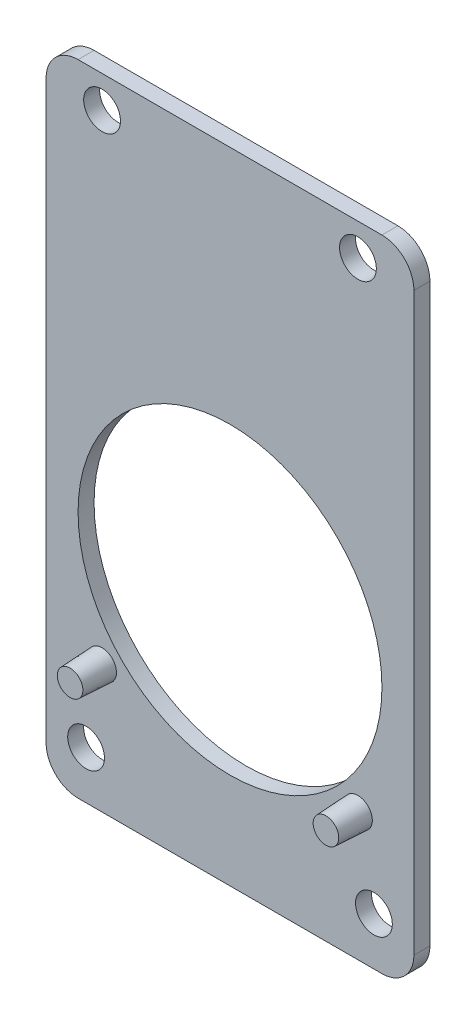
SolidWorks part; units mm, degrees
ref_plane "前视基准面" through (0, 0, 0) normal (0, 0, 1) x (1, 0, 0)
ref_plane "上视基准面" through (0, 0, 0) normal (0, 1, 0) x (1, 0, 0)
ref_plane "右视基准面" through (0, 0, 0) normal (1, 0, 0) x (0, 0, -1)
sketch "草图1" plane through (0, 0, 0) normal (0, 0, 1) x (1, 0, 0)
  line L0 (0, -4.5) -> (0, 11.0108) construction
  line L1 (-11.5, -20) -> (11.5, -20)
  line L2 (-11.5, -20) -> (-11.5, 20)
  line L3 (-11.5, 20) -> (11.5, 20)
  line L4 (11.5, -20) -> (11.5, 20)
  line L5 (-11.5, -20) -> (11.5, 20) construction
  line L6 (-11.5, 20) -> (11.5, -20) construction
  circle A0 centre (0, -4.5) radius 9.5
  point P0 (0, 0)
  dimension "D3" = 19
  dimension "D4" = 15.5
  dimension "D1" = 23
  dimension "D2" = 40
extrude "凸台-拉伸1" add sketch "草图1" along normal blind 1
fillet "圆角1" radius 2 4 edges at (-11.5, -20, 0.5) (11.5, -20, 0.5) (-11.5, 20, 0.5) (11.5, 20, 0.5)
sketch "草图3" plane through (0, 0, 1) normal (0, 0, 1) x (1, 0, 0)
  line L0 (0, 0) -> (0, 20.9871) construction
  line L1 (0, 0) -> (0, -21.9246) construction
  line L2 (9.5, 20) -> (-9.5, 20) construction
  line L3 (-9.5, -20) -> (9.5, -20) construction
  circle A0 centre (-8, 18) radius 1.15
  circle A1 centre (8, 18) radius 1.15
  circle A2 centre (-9, -17) radius 1.15
  circle A3 centre (9, -17) radius 1.15
  dimension "D1" = 2.3
  dimension "D2" = 2.3
  dimension "D4" = 3
  dimension "D6" = 18
  dimension "D3" = 2
  dimension "D5" = 16
extrude "切除-拉伸1" cut sketch "草图3" against normal through all
sketch "草图4" plane through (0, 0, 1) normal (0, 0, 1) x (1, 0, 0)
  line L0 (0, 0) -> (0, -9.2684) construction
  line L1 (-9.5, -20) -> (9.5, -20) construction
  circle A0 centre (-8, -12) radius 0.9
  circle A1 centre (8, -12) radius 0.9
  point P9 (0, -0.3729)
  dimension "D1" = 1.8
  dimension "D2" = 8
  dimension "D3" = 8
extrude "凸台-拉伸2" add sketch "草图4" along normal blind 2
chamfer "倒角1" distance 2 distance2 0.1 2 edges at (8.9, -12, 3) (-7.1, -12, 3) first distance on face at (8.9, -12, 3) first distance on face at (-7.1, -12, 3)
